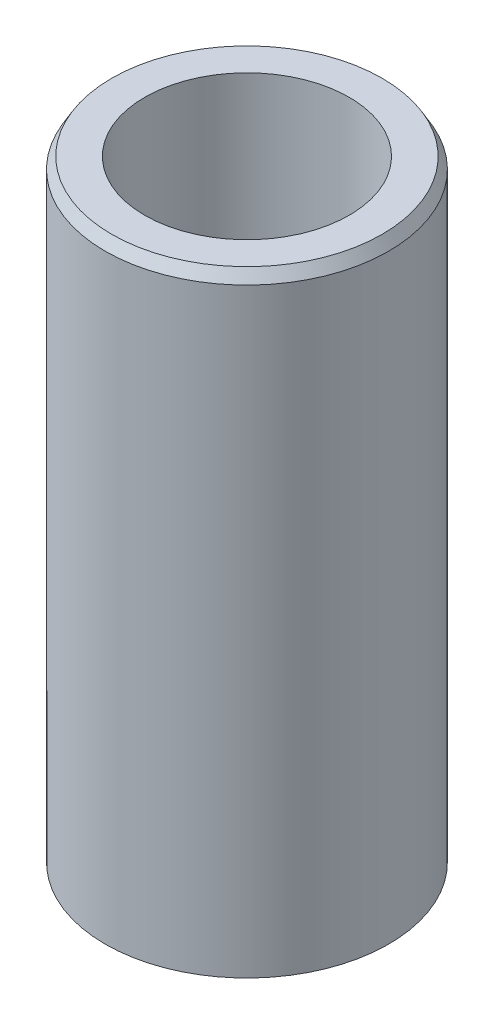
SolidWorks part; units mm, degrees
ref_plane "Front Plane" through (0, 0, 0) normal (0, 0, 1) x (1, 0, 0)
ref_plane "Top Plane" through (0, 0, 0) normal (0, 1, 0) x (1, 0, 0)
ref_plane "Right Plane" through (0, 0, 0) normal (1, 0, 0) x (0, 0, -1)
sketch "Sketch1" plane through (0, 0, 0) normal (0, 1, 0) x (1, 0, 0)
  circle A0 centre (0, 0) radius 57.5
  dimension "SHAFT_OD" = 115
extrude "Boss-Extrude1" add sketch "Sketch1" along normal blind 250.6818
sketch "Sketch2" plane through (0, 0, 0) normal (0, 1, 0) x (1, 0, 0)
  circle A0 centre (0, 0) radius 41.477
  dimension "BORE_D" = 82.9539
extrude "Cut-Extrude1" cut sketch "Sketch2" along normal through all
chamfer "Chamfer1" distance 4.5993 angle 30 2 edges at (0, 250.6818, 57.5) (0, 0, 57.5) first distance on face at (0, 250.6818, 57.5) first distance on face at (0, 0, 41.477)
